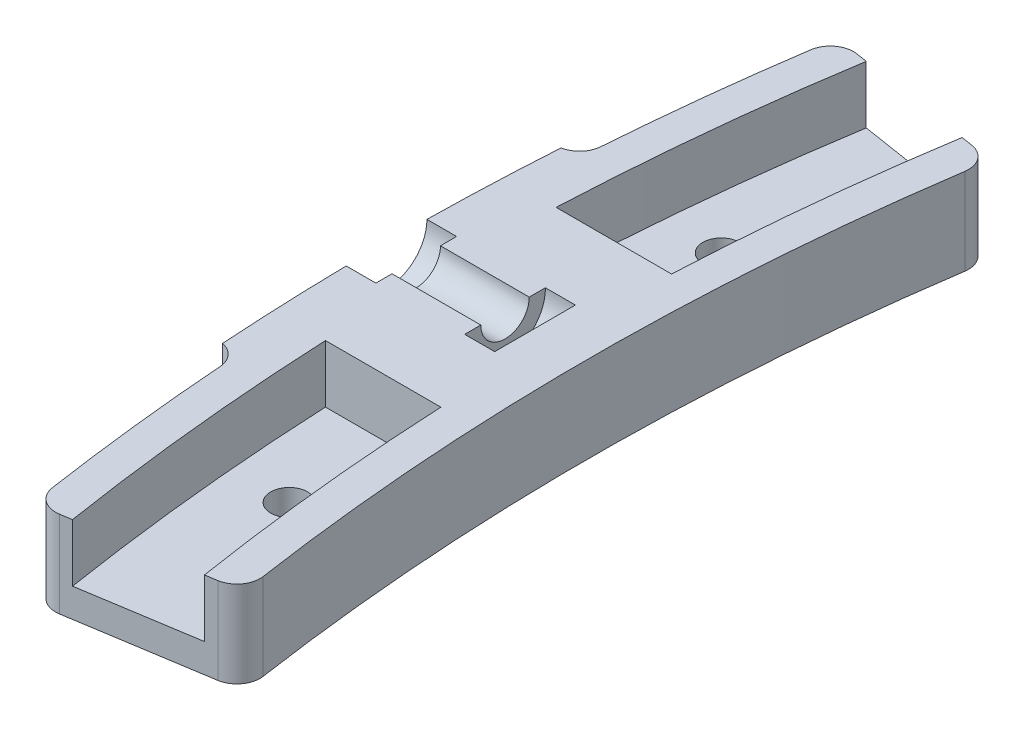
SolidWorks part; units mm, degrees
ref_plane "Front Plane" through (0, 0, 0) normal (0, 0, 1) x (1, 0, 0)
ref_plane "Top Plane" through (0, 0, 0) normal (0, 1, 0) x (1, 0, 0)
ref_plane "Right Plane" through (0, 0, 0) normal (1, 0, 0) x (0, 0, -1)
sketch "Sketch1" plane through (0, 0, 0) normal (0, 1, 0) x (1, 0, 0)
  line L0 (0, 0) -> (-217.2914, -34.4156) construction
  line L1 (0, 0) -> (-217.2914, 34.4156) construction
  line L2 (0, 0) -> (-215, 0) construction
  line L3 (-217.2914, 34.4156) -> (-207.4146, 32.8512)
  line L4 (-207.4146, -32.8512) -> (-217.2914, -34.4156)
  line L5 (0, 0) -> (-220.2545, -34.8849) construction
  line L6 (0, 0) -> (-220.2545, 34.8849) construction
  line L7 (-220.2545, 34.8849) -> (-204.4515, 32.3819)
  line L8 (-220.2545, -34.8849) -> (-204.4515, -32.3819)
  arc A0 (-217.2914, 34.4156) -> (-217.2914, -34.4156) centre (0, 0) ccw
  arc A1 (-207.4146, 32.8512) -> (-207.4146, -32.8512) centre (0, 0) ccw
  arc A2 (-212.353, -33.6334) -> (-212.353, 33.6334) centre (0, 0) cw construction
  arc A4 (-204.4515, 32.3819) -> (-204.4515, -32.3819) centre (0, 0) ccw
  arc A5 (-220.2545, 34.8849) -> (-220.2545, -34.8849) centre (0, 0) ccw
  dimension "D1" = 220
  dimension "D2" = 210
  dimension "D3" = 5
  dimension "D5" = 207
  dimension "D6" = 223
  dimension "D4" = 18
extrude "Boss-Extrude1" add sketch "Sketch1" along normal blind 7.5 contours A1 L3 A0 L4 | L7 A5 L8 A0 | A4 L7 A1 L8
ref_plane "Plane1" through (-215, 0, 0) normal (1, 0, 0) x (0, 0, -1)
sketch "Sketch19" plane through (0, 0, 0) normal (0, 1, 0) x (1, 0, 0)
  line L0 (0, 0) -> (-224.0193, 14.683) construction
  line L1 (0, 0) -> (-224.0193, -14.683) construction
  line L4 (0, 0) -> (-224.5, 0) construction
  line L5 (-224.0193, 14.683) -> (-222.5225, 14.5849)
  line L6 (-224.0193, -14.683) -> (-222.5225, -14.5849)
  arc A0 (-224.0193, 14.683) -> (-224.0193, -14.683) centre (0, 0) ccw
  arc A1 (-220.2545, 34.8849) -> (-220.2545, -34.8849) centre (0, 0) ccw construction
  arc A2 (-222.5225, 14.5849) -> (-222.5225, -14.5849) centre (0, 0) ccw
  dimension "D1" = 224.5
  dimension "D2" = 3.75
extrude "Boss-Extrude2" add sketch "Sketch19" along normal blind 7.5
sketch "Sketch15" plane through (0, 7.5, 0) normal (0, 1, 0) x (1, 0, 0)
  line L0 (-207.4146, -32.8512) -> (-217.2914, -34.4156) construction
  line L1 (-205, 10) -> (-225, 10)
  line L2 (-205, 10) -> (-205, -10)
  line L3 (-205, -10) -> (-225, -10)
  line L4 (-225, 10) -> (-225, -10)
  line L5 (-205, 10) -> (-225, -10) construction
  line L6 (-205, -10) -> (-225, 10) construction
  line L7 (-217.2914, 34.4156) -> (-207.4146, 32.8512) construction
  line L8 (-207.4146, -32.8512) -> (-217.2914, -34.4156)
  line L9 (-217.2914, 34.4156) -> (-207.4146, 32.8512)
  arc A2 (-207.4146, 32.8512) -> (-207.4146, -32.8512) centre (0, 0) ccw construction
  arc A3 (-217.2914, 34.4156) -> (-217.2914, -34.4156) centre (0, 0) ccw construction
  arc A4 (-207.4146, 32.8512) -> (-207.4146, -32.8512) centre (0, 0) ccw
  arc A5 (-217.2914, 34.4156) -> (-217.2914, -34.4156) centre (0, 0) ccw
  point P0 (-215, 0)
  line M5 (-220.2545, -34.8849) -> (-204.4515, -32.3819)
  line M7 (-204.4515, 32.3819) -> (-220.2545, 34.8849)
  dimension "D1" = 20
  dimension "D2" = 20
extrude "Cut-Extrude1" cut sketch "Sketch15" against normal blind 5 contours A5 L1 A4 M7 | L3 A5 A4 M5
ref_plane "Plane2" through (-215, 0, 0) normal (-1, 0, 0) x (0, 0, 1)
sketch "Sketch12" plane through (0, 0, 0) normal (0, 1, 0) x (1, 0, 0)
  line L0 (0, 0) -> (-214.1819, -18.7385) construction
  line L1 (0, 0) -> (-213.1606, -28.0631) construction
  line L2 (0, 0) -> (-215, 0) construction
  line L3 (0, 0) -> (-215, 0) construction
  line L4 (0, 0) -> (-214.1819, 18.7385) construction
  line L5 (0, 0) -> (-213.1606, 28.0631) construction
  arc A0 (-212.353, 33.6334) -> (-212.353, -33.6334) centre (0, 0) ccw construction
  dimension "D1" = 10
  dimension "D2" = 15
hole_wizard "Ø3.2 (3.2) Diameter Hole1" positions "Sketch18" profile "Sketch17" hole size "Ø3.2" standard "ISO" end condition through all
sketch "Sketch18" plane through (0, 0, 0) normal (0, -1, 0) x (-1, 0, 0)
  point P3 (214.1819, -18.7385)
  point P6 (214.1819, 18.7385)
  point P13 (0, 0)
  point P14 (0, 0)
sketch "Sketch17" plane through (-214.1819, 0, 18.7385) normal (1, 0, 0) x (0, 0, -1)
  line L0 (0, 0) -> (0, 7.5)
  line L1 (0, 7.5) -> (1.6, 7.5)
  line L2 (1.6, 7.5) -> (1.6, 0)
  line L5 (1.6, 0) -> (0, 0)
  line L11 (0, -6.35) -> (0, 107.95) construction
  dimension "Thru Hole Dia." = 3.2
  dimension "Thru Hole Depth" = 7.5
sketch "Sketch20" plane through (0, 0, 0) normal (0, 1, 0) x (1, 0, 0)
  line L0 (-205, 0) -> (-192.5, 0) construction
  line L1 (0, 0) -> (-205, 0) construction
  arc A2 (-224.0193, 14.683) -> (-224.0193, -14.683) centre (0, 0) ccw construction
  point P3 (-224.5, 0)
  dimension "D1" = 205
  dimension "D2" = 12.5
ref_plane "Plane3" through (-192.5, 0, 0) normal (1, 0, 0) x (0, 0, -1)
ref_plane "Plane4" through (-224.5, 0, 0) normal (1, 0, 0) x (0, 0, -1)
fillet "Fillet1" radius 2 4 edges at (-220.2545, 3.75, -34.8849) (-204.4515, 3.75, -32.3819) (-204.4515, 3.75, 32.3819) (-220.2545, 3.75, 34.8849)
fillet "Fillet2" radius 2 2 edges at (-222.5225, 3.75, -14.5849) (-222.5225, 3.75, 14.5849)
sketch "Sketch21" plane through (0, 7.5, 0) normal (0, 1, 0) x (1, 0, 0)
  line L0 (-225, 0) -> (0, 0) construction
  line L1 (-225, 0) -> (-212.5, 0) construction
  dimension "D1" = 225
  dimension "D2" = 12.5
ref_plane "Plane5" through (-212.5, 0, 0) normal (1, 0, 0) x (0, 0, -1)
sketch "Sketch22" plane through (-212.5, 0, 0) normal (1, 0, 0) x (0, 0, -1)
  line L0 (30.424, 7.5) -> (-30.424, 7.5) construction
  circle A0 centre (0, 7.5) radius 2.1
  dimension "D1" = 4.2
extrude "Cut-Extrude2" cut sketch "Sketch22" against normal through all and the other way up to surface (0.9 mm away)
sketch "Sketch23" plane through (-211.6, 0, 0) normal (-1, 0, 0) x (0, 0, 1)
  circle A0 centre (0, 7.4392) radius 3.5
  dimension "D1" = 7
extrude "Cut-Extrude3" cut sketch "Sketch23" along normal blind 2.6
sketch "Sketch24" plane through (0, 7.5, 0) normal (0, 1, 0) x (1, 0, 0)
  line L0 (-224.5, 0) -> (-207, 0) construction
  line L2 (-224.5, 0) -> (-221.9, 0)
  line L3 (-224.5, 0) -> (-224.5, 3.5)
  line L4 (-224.5, 3.5) -> (-221.9, 3.5)
  line L5 (-221.9, 0) -> (-221.9, 3.5)
  arc A0 (-224.4902, 2.1) -> (-224.4902, -2.1) centre (0, 0) ccw construction
  arc A1 (-204.752, 30.424) -> (-204.752, -30.424) centre (0, 0) ccw construction
  dimension "D1" = 2.6
  dimension "D2" = 7
revolve "Cut-Revolve1" cut sketch "Sketch24" angle 360 about L0
